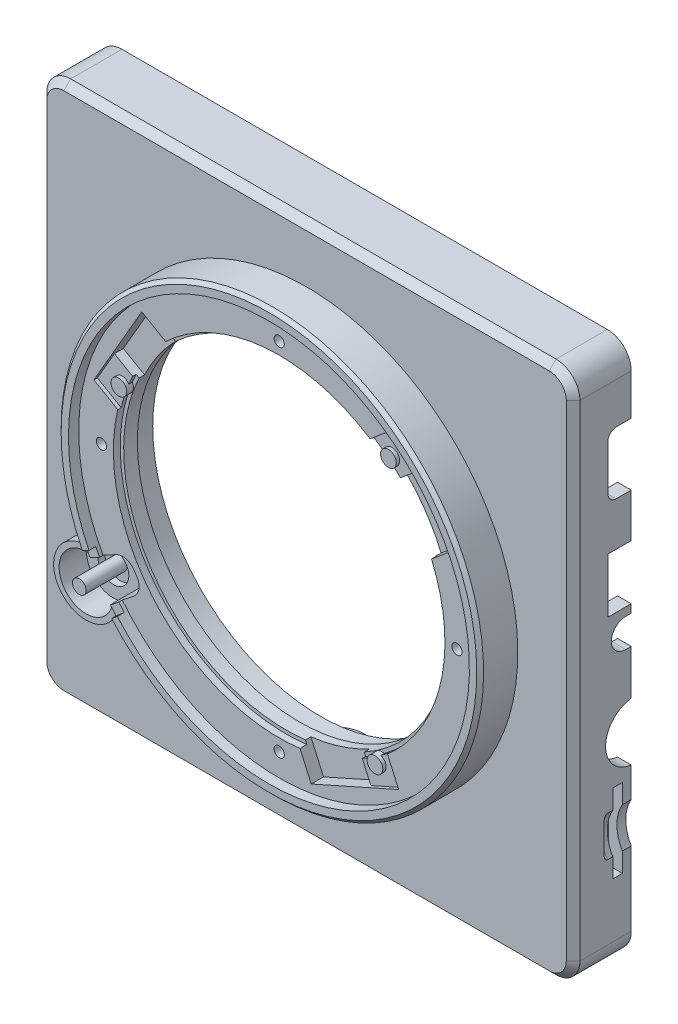
SolidWorks part; units mm, degrees
ref_plane "前视基准面" through (0, 0, 0) normal (0, 0, 1) x (1, 0, 0)
ref_plane "上视基准面" through (0, 0, 0) normal (0, 1, 0) x (1, 0, 0)
ref_plane "右视基准面" through (0, 0, 0) normal (1, 0, 0) x (0, 0, -1)
other "Configuration Table"
sketch "草图1" plane through (0, 0, 0) normal (0, 0, 1) x (1, 0, 0)
  line L1 (-39, -39) -> (39, -39)
  line L2 (-39, -39) -> (-39, 39)
  line L3 (-39, 39) -> (39, 39)
  line L4 (39, -39) -> (39, 39)
  line L5 (-39, -39) -> (39, 39) construction
  line L6 (-39, 39) -> (39, -39) construction
  circle A0 centre (0, 0) radius 23.75
  point P0 (0, 0)
  dimension "D2" = 47.5
  dimension "D1" = 78
extrude "凸台-拉伸1" add sketch "草图1" against normal blind 2
sketch "草图2" plane through (0, 0, 0) normal (0, 0, 1) x (1, 0, 0)
  circle A0 centre (0, 0) radius 23.75
  circle A1 centre (0, 0) radius 23.75 construction
  circle A2 centre (0, 0) radius 30.9
  dimension "D1" = 61.8
extrude "凸台-拉伸2" add sketch "草图2" along normal blind 4
sketch "草图3" plane through (0, 0, -2) normal (0, 0, -1) x (-1, 0, 0)
  line L0 (35.5, 32) -> (35.5, -32)
  line L1 (-39, -39) -> (39, -39)
  line L2 (-39, -39) -> (-39, 39)
  line L3 (-39, 39) -> (39, 39)
  line L4 (39, -39) -> (39, 39)
  line L5 (-39, -39) -> (39, 39) construction
  line L6 (-39, 39) -> (39, -39) construction
  line L7 (-37, -37) -> (37, -37)
  line L8 (-37, -37) -> (-37, 37)
  line L9 (-37, 37) -> (37, 37)
  line L10 (37, -37) -> (37, 37)
  line L11 (-37, -37) -> (37, 37) construction
  line L12 (-37, 37) -> (37, -37) construction
  line L13 (-37, 37) -> (-32, 37)
  line L14 (-37, 37) -> (-37, 32)
  line L15 (-37, 32) -> (-32, 32)
  line L16 (-32, 37) -> (-32, 32)
  line L17 (37, 37) -> (32, 37)
  line L18 (37, 37) -> (37, 32)
  line L19 (37, 32) -> (32, 32)
  line L20 (32, 37) -> (32, 32)
  line L21 (-37, -37) -> (-32, -37)
  line L22 (-37, -37) -> (-37, -32)
  line L23 (-37, -32) -> (-32, -32)
  line L24 (-32, -37) -> (-32, -32)
  line L25 (37, -37) -> (32, -37)
  line L26 (37, -37) -> (37, -32)
  line L27 (37, -32) -> (32, -32)
  line L28 (32, -37) -> (32, -32)
  point P0 (0, 0)
  point P7 (0, 0)
  line M23 (-39, 39) -> (-39, -39)
  line M24 (-39, -39) -> (39, -39)
  line M25 (39, -39) -> (39, 39)
  line M26 (39, 39) -> (-39, 39)
  dimension "D1" = 2
  dimension "D2" = 5
  dimension "D3" = 1.5
extrude "凸台-拉伸3" add sketch "草图3" along normal blind 6.5 contours L10 L7 L8 L9 M26 M23 M24 M25 | L16 L9 L8 L15 | L9 L20 L19 L10 | L28 L7 L10 L27 | L7 L24 L23 L8 | L27 L10 L19 L0 region at (-36.25, 0, -2) region at (-34.5, 34.5, -2) region at (-34.5, -34.5, -2) region at (34.5, 34.5, -2) region at (34.5, -34.5, -2) region at (37.8969, 0, -2)
sketch "草图4" plane through (0, 0, 4) normal (0, 0, 1) x (1, 0, 0)
  line L0 (0, 26) -> (0, -26) construction
  line L1 (-26, 0) -> (26, 0) construction
  circle A0 centre (0, 0) radius 26 construction
  circle A1 centre (0, 26) radius 0.75
  circle A2 centre (26, 0) radius 0.75
  circle A3 centre (0, -26) radius 0.75
  circle A4 centre (-26, 0) radius 0.75
  dimension "D2" = 52
  dimension "D3" = 1.5
extrude "切除-拉伸1" cut sketch "草图4" against normal blind 5
sketch "草图5" plane through (0, 0, 4) normal (0, 0, 1) x (1, 0, 0)
  line L0 (-15.4397, 0) -> (13.8511, 0) construction
  line L1 (-27.9748, -13.7193) -> (-23.5593, -20.3904)
  line L2 (-23.5593, -20.3904) -> (0, 0) construction
  line L3 (0, 0) -> (-27.9748, -13.7193) construction
  line L4 (-25.7671, -17.0549) -> (0, 0) construction
  line L5 (-27.9748, -13.7193) -> (-26.8884, -13.1865)
  line L6 (-26.8884, -13.1865) -> (-26.2006, -14.2257)
  line L7 (-26.2006, -14.2257) -> (0, 0) construction
  line L8 (0, 0) -> (-23.3322, -18.5593) construction
  line L9 (-23.3322, -18.5593) -> (-22.6444, -19.5985)
  line L10 (-22.6444, -19.5985) -> (-23.5593, -20.3904)
  line L11 (-26.2006, -14.2257) -> (-23.8565, -12.953)
  line L12 (-21.2344, -13.6068) -> (-20.822, -14.2298)
  line L13 (-21.2448, -16.8989) -> (-23.3322, -18.5593)
  circle A0 centre (0, 0) radius 30.9 construction
  arc A1 (-20.822, -14.2298) -> (-21.2448, -16.8989) centre (-22.4898, -15.3336) cw
  arc A2 (-23.8565, -12.953) -> (-21.2344, -13.6068) centre (-22.9021, -14.7106) cw
  point P17 (-19.8105, -15.758)
  point P20 (-22.2459, -12.0785)
  dimension "D6" = 2
  dimension "D1" = 33.5
  dimension "D2" = 8
  dimension "D3" = 5
  dimension "D4" = 1.2
  dimension "D5" = 4.5
extrude "切除-拉伸2" cut sketch "草图5" against normal blind 4
sketch "草图8" plane through (0, 0, 4) normal (0, 0, 1) x (1, 0, 0)
  line L0 (-27.7433, -13.6058) -> (-26.3292, -12.9123)
  line L1 (-23.3644, -20.2217) -> (-22.1735, -19.191)
  circle A0 centre (0, 0) radius 30.9
  circle A1 centre (0, 0) radius 29.325
  arc A2 (-23.3644, -20.2217) -> (-27.7433, -13.6058) centre (0, 0) ccw construction
  line M27 (-27.7433, -13.6058) -> (-26.8884, -13.1865)
  line M35 (-22.6444, -19.5985) -> (-23.3644, -20.2217)
  arc M36 (-23.3644, -20.2217) -> (-27.7433, -13.6058) centre (0, 0) ccw
  dimension "D1" = 58.65
extrude "凸台-拉伸5" add sketch "草图8" along normal blind 1.5 contours A1 L1 L0 M35 M36 M27 region at (-6.7861, 29.2491, 4)
chamfer "倒角1" distance 0.5 angle 45 1 edges at (25.7671, 17.0549, 5.5)
sketch "草图9" plane through (0, 0, -2) normal (0, 0, -1) x (-1, 0, 0)
  line L1 (-19, -20) -> (19, -20) construction
  line L2 (-19, -20) -> (-19, 20) construction
  line L3 (-19, 20) -> (19, 20) construction
  line L4 (19, -20) -> (19, 20) construction
  line L5 (-19, -20) -> (19, 20) construction
  line L6 (-19, 20) -> (19, -20) construction
  circle A0 centre (-19, -20) radius 0.8
  circle A1 centre (-19, -20) radius 1.65
  circle A2 centre (-19, 20) radius 0.8
  circle A3 centre (-19, 20) radius 1.65
  circle A4 centre (19, 20) radius 0.8
  circle A5 centre (19, 20) radius 1.65
  point P0 (0, 0)
  dimension "D2" = 1.6
  dimension "D3" = 3.3
  dimension "D1" = 38
  dimension "D4" = 40
extrude "凸台-拉伸6" add sketch "草图9" along normal blind 2.1
extrude "切除-拉伸4" cut sketch "草图9<2>" against normal blind 2 contours A2 | A4 | A0 region at (19, -20, -2) region at (19, 20, -2) region at (-19, 20, -2)
sketch "草图9<2>" plane through (0, 0, -2) normal (0, 0, -1) x (-1, 0, 0) same geometry as "草图9"
sketch "草图10" plane through (0, 0, -8.5) normal (0, 0, -1) x (-1, 0, 0)
  line L0 (39, 39) -> (-39, 39) construction
  line L1 (34.5, -34.5) -> (-34.5, -34.5) construction
  line L2 (34.5, -34.5) -> (34.5, 34.5) construction
  line L3 (34.5, 34.5) -> (-34.5, 34.5) construction
  line L4 (-34.5, -34.5) -> (-34.5, 34.5) construction
  line L5 (34.5, -34.5) -> (-34.5, 34.5) construction
  line L6 (34.5, 34.5) -> (-34.5, -34.5) construction
  circle A0 centre (-34.5, 34.5) radius 0.8
  circle A1 centre (34.5, 34.5) radius 0.8
  circle A2 centre (34.5, -34.5) radius 0.8
  circle A3 centre (-34.5, -34.5) radius 0.8
  point P0 (0, 0)
  dimension "D2" = 1.6
  dimension "D1" = 4.5
extrude "切除-拉伸5" cut sketch "草图10" against normal blind 4
sketch "草图18" plane through (0, -39, 0) normal (0, -1, 0) x (1, 0, 0)
  line L0 (39, -8.5) -> (-39, -8.5) construction
  line L1 (-39, 0) -> (39, 0) construction
  circle A0 centre (0, -4.25) radius 4.25
  circle A1 centre (0, -4.25) radius 2.5527
  dimension "D1" = 5.1054
extrude "凸台-拉伸9" add sketch "草图18" against normal blind 9 contours A1 | A0 A1 region at (-4.1298, -39, -4.25) region at (0, -39, -4.25)
extrude "切除-拉伸9" cut sketch "草图18<4>" against normal blind 7.5 contours A1 region at (0, -39, -4.25)
sketch "草图18<4>" plane through (0, -39, 0) normal (0, -1, 0) x (1, 0, 0) same geometry as "草图18"
sketch "草图30" plane through (0, 0, 0) normal (0, 0, 1) x (1, 0, 0)
  line L0 (-22.39, -14.8196) -> (0, 0) construction
  line L1 (-26.8884, -13.1865) -> (-28.4451, -13.9499)
  line L2 (-26.2006, -14.2257) -> (-27.3486, -14.8491)
  line L3 (-23.3322, -18.5593) -> (-24.3546, -19.3725)
  line L4 (-22.6444, -19.5985) -> (-23.9553, -20.7332)
  line L5 (-22.6444, -19.5985) -> (-23.3322, -18.5593)
  line L6 (-23.3644, -20.2217) -> (-22.6444, -19.5985) construction
  line L7 (-23.3322, -18.5593) -> (-21.2448, -16.8989) construction
  line L8 (-23.8565, -12.953) -> (-26.2006, -14.2257) construction
  line L9 (-27.2944, -13.3856) -> (-26.3292, -12.9123) construction
  line L10 (-26.8884, -13.1865) -> (-26.2006, -14.2257)
  line L11 (-20.822, -14.2298) -> (-21.2344, -13.6068) construction
  line L12 (-20.822, -14.2298) -> (-21.2344, -13.6068) construction
  circle A0 centre (-28.2462, -18.6958) radius 4.75
  circle A2 centre (-28.2462, -18.6958) radius 3.95
  point P3 (-21.0282, -13.9183)
  line M13 (-26.8884, -13.1865) -> (-27.7433, -13.6058)
  line M15 (-23.3644, -20.2217) -> (-22.6444, -19.5985)
  line M16 (-22.6444, -19.5985) -> (-23.3322, -18.5593)
  line M22 (-26.2006, -14.2257) -> (-26.8884, -13.1865)
  dimension "D2" = 9.5
  dimension "D3" = 7.9
  dimension "D1" = 33.873
extrude "凸台-拉伸10" add sketch "草图30" along normal blind 4 contours A0 L2 L1 M22 M13 | A0 L0 A2 L2 | L0 A0 L3 A2 | A0 L4 L3 M15 M16 region at (-27.1202, -13.7897, 0) region at (-27.418, -14.155, 0) region at (-23.2902, -19.5762, 0)
sketch "草图31" plane through (0, 0, 0) normal (0, 0, 1) x (1, 0, 0)
  circle A0 centre (-28.2462, -18.6958) radius 1
  circle A1 centre (-28.2462, -18.6958) radius 2.25
  dimension "D1" = 2
  dimension "D2" = 4.5
extrude "切除-拉伸19" cut sketch "草图31" against normal blind 1
sketch "草图32" plane through (0, 0, 0) normal (0, 0, 1) x (1, 0, 0)
  circle A0 centre (-28.2462, -18.6958) radius 1
  circle A1 centre (-28.2462, -18.6958) radius 1 construction
extrude "凸台-拉伸11" add sketch "草图32" along normal blind 5
sketch "草图33" plane through (0, 0, 4) normal (0, 0, 1) x (1, 0, 0)
  line L0 (-26.3292, -12.9123) -> (-27.7433, -13.6058)
  line L1 (-27.1554, -14.7442) -> (-25.7713, -13.9927)
  line L2 (-23.8565, -12.953) -> (-27.3486, -14.8491) construction
  line L3 (-23.8565, -12.953) -> (-27.3486, -14.8491) construction
  line L4 (-24.1826, -19.2357) -> (-22.95, -18.2552)
  line L5 (-24.3546, -19.3725) -> (-21.2448, -16.8989) construction
  line L6 (-22.1735, -19.191) -> (-23.3644, -20.2217)
  circle A0 centre (0, 0) radius 29.325
  circle A1 centre (0, 0) radius 30.9
  line M3 (-26.3292, -12.9123) -> (-27.7433, -13.6058)
  line M7 (-23.3644, -20.2217) -> (-22.1735, -19.191)
  line M10 (-27.3486, -14.8491) -> (-23.8565, -12.953)
  line M14 (-21.2448, -16.8989) -> (-24.3546, -19.3725)
extrude "凸台-拉伸12" add sketch "草图33" along normal blind 0.5 contours A1 A0 M3 M10 | A1 A0 M14 M7 region at (-26.7598, -13.8189, 4) region at (-23.1762, -19.233, 4)
fillet "圆角5" radius 1 2 edges at (-3.6056, -33.5, -2) (3.6056, -33.5, -2)
fillet "圆角2" radius 1.5 12 edges at (37, -32, -5.25) (32, -37, -5.25) (-32, -37, -5.25) (-32, -32, -5.25) (-32, 37, -5.25) (32, -32, -5.25) (-32, 32, -5.25) (32, 37, -5.25) (37, 32, -5.25) (32, 32, -5.25) (-35.5, -32, -5.25) (-35.5, 32, -5.25)
fillet "圆角3" radius 3.5 4 edges at (39, -39, -4.25) (-39, -39, -4.25) (-39, 39, -4.25) (39, 39, -4.25)
chamfer "倒角2" distance 1 angle 45 8 edges at (0, -39, 0) (37.9749, -37.9749, 0) (-37.9749, -37.9749, 0) (39, 0, 0) (-39, 0, 0) (37.9749, 37.9749, 0) (-37.9749, 37.9749, 0) (0, 39, 0)
sketch "草图11" plane through (0, 0, 4) normal (0, 0, 1) x (1, 0, 0)
  circle A0 centre (0, 0) radius 24.25
  dimension "D1" = 48.5
extrude "切除-拉伸6" cut sketch "草图11" against normal blind 1
sketch "草图19" plane through (-39, 0, 0) normal (-1, 0, 0) x (0, 0, 1)
  line L0 (-8.5, -35.5) -> (-8.5, 35.5) construction
  line L1 (-8.5, 30) -> (-2.5, 30)
  line L2 (-8.5, 30) -> (-8.5, -30)
  line L3 (-8.5, -30) -> (-2.5, -30)
  line L4 (-2.5, 30) -> (-2.5, -30)
  line L5 (-10.4781, 0) -> (-27.7758, 0) construction
  dimension "D1" = 6
  dimension "D2" = 60
extrude "切除-拉伸10" cut sketch "草图19" against normal blind 1.8
sketch "草图12" plane through (0, 0, -8.5) normal (0, 0, -1) x (-1, 0, 0)
  line L0 (-30.5, 37) -> (30.5, 37) construction
  line L1 (-14.5, 37) -> (14.5, 37)
  line L2 (-14.5, 37) -> (-14.5, 38)
  line L3 (-14.5, 38) -> (14.5, 38)
  line L4 (14.5, 37) -> (14.5, 38)
  line L10 (-30.5, -37) -> (-5.099, -37) construction
  line L11 (14.5, -37) -> (-14.5, -37)
  line L12 (14.5, -37) -> (14.5, -38)
  line L13 (14.5, -38) -> (-14.5, -38)
  line L14 (-14.5, -37) -> (-14.5, -38)
  line L20 (0, -4.6052) -> (0, 11.8131) construction
  line L21 (9.1859, 0) -> (-14.9207, 0) construction
  line L22 (-3.5, -37) -> (-3.5, -38)
  line L23 (3.5, -37) -> (3.5, -38)
  line M27 (30.5, -37) -> (0, -37)
  line M39 (-30.5, 37) -> (30.5, 37)
  dimension "D1" = 29
  dimension "D2" = 1
  dimension "D3" = 7
extrude "切除-拉伸7" cut sketch "草图12" against normal blind 1 contours L22 L11 L14 L13 | L23 L13 L12 M27 | L4 L3 L2 M39
sketch "草图21" plane through (0, 0, -2) normal (0, 0, -1) x (-1, 0, 0)
  circle A0 centre (0, 0) radius 24.5
  dimension "D1" = 49
extrude "切除-拉伸12" cut sketch "草图21" against normal blind 3
sketch "草图22" plane through (0, 0, 0) normal (0, 0, 1) x (1, 0, 0)
  text T0 "Sitina" font "Corbel" height 3.5
  text T1 "S1" font "Sylfaen" height 3.5
sketch "草图23" plane through (0, 0, -8.5) normal (0, 0, -1) x (-1, 0, 0)
  line L0 (35.5, 30.5) -> (35.5, -30.5) construction
  line L1 (35.5, 20) -> (37.2, 20)
  line L2 (35.5, 20) -> (35.5, 10.5)
  line L3 (35.5, 10.5) -> (37.2, 10.5)
  line L4 (37.2, 20) -> (37.2, 10.5)
  line L5 (37.2, -30) -> (37.2, 30) construction
  dimension "D1" = 9.5
  dimension "D2" = 10.5
extrude "切除-拉伸14" cut sketch "草图23" against normal blind 1
sketch "草图24" plane through (-35.5, 0, 0) normal (1, 0, 0) x (0, 0, -1)
  line L0 (4.7, -23.516) -> (4.7, -0.4558) construction
  line L1 (8.5, 10.5) -> (8.5, -30.5) construction
  line L2 (2, -30.5) -> (8.5, -30.5) construction
  line L3 (4.7, -25) -> (4.7, 0) construction
  circle A0 centre (4.7, -25) radius 0.65
  circle A1 centre (4.7, 0) radius 0.65
  circle A2 centre (4.7, 25) radius 0.65
  dimension "D2" = 1.3
  dimension "D1" = 3.8
  dimension "D3" = 5.5
  dimension "D5" = 25
  dimension "D4" = 3
extrude "切除-拉伸15" cut sketch "草图24" against normal blind 4.75
sketch "草图26" plane through (39, 0, 0) normal (1, 0, 0) x (0, 0, -1)
  line L0 (8.5, 35.5) -> (8.5, -35.5) construction
  line L1 (5.8, -27.5) -> (7.2, -27.5)
  line L2 (5.8, -27.5) -> (5.8, -16)
  line L3 (5.8, -16) -> (7.2, -16)
  line L4 (7.2, -27.5) -> (7.2, -16)
  line L5 (1, -35.5) -> (8.5, -35.5) construction
  line L6 (12.7, 2.7) -> (7.7, 2.7) construction
  line L7 (12.7, 0.6) -> (7.7, 0.6)
  line L8 (12.7, 4.8) -> (7.7, 4.8)
  line L9 (8.5, 29.5) -> (8.5, 20.4)
  line L12 (8.5, 35.5) -> (1, 35.5) construction
  line L13 (8.5, 20.4) -> (6.3, 20.4)
  line L14 (8.5, 29.5) -> (6.3, 29.5)
  line L15 (5.1, 28.3) -> (5.1, 21.6)
  line L17 (8.5, 14) -> (5.1, 14)
  line L18 (8.5, 14) -> (8.5, 6)
  line L19 (8.5, 6) -> (5.1, 6)
  line L20 (5.1, 14) -> (5.1, 6)
  circle A0 centre (9, -10.2) radius 4.25
  arc A1 (12.7, 0.6) -> (12.7, 4.8) centre (12.7, 2.7) ccw
  arc A2 (7.7, 4.8) -> (7.7, 0.6) centre (7.7, 2.7) ccw
  arc A5 (6.3, 29.5) -> (5.1, 28.3) centre (6.3, 28.3) ccw
  arc A6 (6.3, 20.4) -> (5.1, 21.6) centre (6.3, 21.6) cw
  point P10 (10.2, 2.7)
  dimension "D7" = 8.5
  dimension "D9" = 2.1
  dimension "D15" = 1.2
  dimension "D1" = 11.5
  dimension "D2" = 1.4
  dimension "D3" = 1.3
  dimension "D4" = 8
  dimension "D5" = 25.3
  dimension "D6" = 0.5
  dimension "D8" = 38.2
  dimension "D10" = 0.8
  dimension "D11" = 5
  dimension "D12" = 6
  dimension "D13" = 9.1
  dimension "D14" = 3.4
  dimension "D16" = 21.5
  dimension "D17" = 8
  dimension "D18" = 3.4
extrude "切除-拉伸17" cut sketch "草图26" against normal blind 10
sketch "草图29" plane through (0, 0, -2) normal (0, 0, -1) x (-1, 0, 0)
  line L0 (0, 6.6658) -> (0, 18.0542) construction
  line L1 (6.3625, 0) -> (19.1145, 0) construction
  circle A0 centre (-15, 22) radius 0.8
  circle A1 centre (15, -22) radius 0.8
  dimension "D1" = 1.6
  dimension "D2" = 15
  dimension "D3" = 15
  dimension "D4" = 22
  dimension "D5" = 22
extrude "切除-拉伸18" cut sketch "草图29" against normal blind 3
fillet "圆角6" radius 0.5 2 edges at (-27.7433, -13.6058, 2) (-23.3644, -20.2217, 2)
sketch "草图34" plane through (0, 0, 4) normal (0, 0, 1) x (1, 0, 0)
  line L0 (15.2413, -17.0225) -> (2.4517, -22.7168)
  line L1 (2.4517, -22.7168) -> (4.6888, -27.7413)
  line L2 (4.6888, -27.7413) -> (17.4784, -22.047)
  line L3 (17.4784, -22.047) -> (15.2413, -17.0225)
  line L4 (0, -1000) -> (0, 49000) construction
  line L5 (0, 0) -> (8.8465, -19.8696) construction
  line L6 (10.6736, -19.0561) -> (12.9107, -24.0806)
  line L7 (12.162, 19.3429) -> (21.161, 8.6183)
  line L8 (21.161, 8.6183) -> (25.3742, 12.1537)
  line L9 (25.3742, 12.1537) -> (16.3752, 22.8783)
  line L10 (16.3752, 22.8783) -> (12.162, 19.3429)
  line L11 (-15.3361, 16.9372) -> (-22.3361, 4.8128)
  line L12 (-22.3361, 4.8128) -> (-27.0992, 7.5628)
  line L13 (-27.0992, 7.5628) -> (-20.0992, 19.6872)
  line L14 (-20.0992, 19.6872) -> (-15.3361, 16.9372)
  line L15 (-24.5992, 11.8929) -> (-19.8361, 9.1429)
  line L16 (15.3759, 15.5127) -> (19.5891, 19.0481)
  line L17 (-18.8361, 10.875) -> (0, 0)
  line L18 (0, 0) -> (16.6615, 13.9806)
  circle A0 centre (0, 0) radius 21.75 construction
  point P5 (8.8465, -19.8696)
  point P19 (-18.8361, 10.875)
  point P22 (16.6615, 13.9806)
  circle M8 centre (0, 0) radius 24.25
  dimension "D1" = 43.5
  dimension "D2" = 14
  dimension "D3" = 5.5
  dimension "D4" = 24
  dimension "D5" = 5
  dimension "D6" = 5
  dimension "D7" = 5
  dimension "D8" = 60
  dimension "D9" = 50
extrude "切除-拉伸20" cut sketch "草图34" against normal blind 0.5 contours L6 L2 L3 M8 | L0 L6 L3 M8 | L16 L9 L10 M8 | L7 L16 L10 M8 | L15 L13 L12 M8 | L15 L12 L11 M8 region at (13.2013, -19.0643, 4) region at (14.5891, -21.424, 4) region at (-21.8858, 7.6638, 4) region at (-24.3955, 8.7571, 4) region at (16.5728, 19.9292, 4) region at (14.687, 17.9447, 4)
extrude "切除-拉伸21" cut sketch "草图34<3>" against normal blind 1.8 contours L6 L0 L1 M8 | L6 L1 L2 M8 | L13 L15 L14 M8 | L15 L11 L14 M8 | L16 L8 L9 M8 | L16 L7 L8 M8 region at (7.314, -21.7939, 4) region at (7.9313, -24.492, 4) region at (21.357, 14.375, 4) region at (18.9336, 13.0379, 4) region at (-18.7273, 13.3326, 4) region at (-20.8126, 15.1525, 4)
sketch "草图34<3>" plane through (0, 0, 4) normal (0, 0, 1) x (1, 0, 0) same geometry as "草图34"
sketch "草图35" plane through (0, 0, 3) normal (0, 0, 1) x (1, 0, 0)
  line L0 (17.4784, -22.047) -> (15.8383, -18.3633) construction
  line L1 (12.9107, -24.0806) -> (17.4784, -22.047) construction
  line L2 (25.3742, 12.1537) -> (16.3752, 22.8783) construction
  line L3 (-27.0992, 7.5628) -> (-20.0992, 19.6872) construction
  line L4 (-23.6071, 5.5467) -> (-27.0992, 7.5628) construction
  line L5 (16.3752, 22.8783) -> (13.2863, 20.2864) construction
  circle A0 centre (14.005, -20.6379) radius 1.15
  circle A1 centre (15.9781, 19.151) radius 1.15
  circle A2 centre (-23.4609, 8.4645) radius 1.15
  dimension "D1" = 2.3
  dimension "D2" = 2.6
  dimension "D3" = 2.7
  dimension "D4" = 2.7
  dimension "D5" = 2.7
  dimension "D6" = 2.6
  dimension "D7" = 2.6
extrude "凸台-拉伸13" add sketch "草图35" along normal blind 1
sketch "草图36" plane through (0, 0, -8.5) normal (0, 0, -1) x (-1, 0, 0)
  line L1 (-1040.6187, -21.75) -> (48959.3813, -21.75) construction
  line L2 (-39, -27.5) -> (-39, -16) construction
  line L3 (-39, -14.4205) -> (-39, -35.5) construction
  circle A0 centre (-44, -21.75) radius 5.8
  point P5 (-39, -21.75)
  dimension "D2" = 11.6
  dimension "D1" = 5
extrude "切除-拉伸22" cut sketch "草图36" against normal blind 4
fillet "圆角7" radius 0.5 1 edges at (38.2, -21.75, -4.5)
